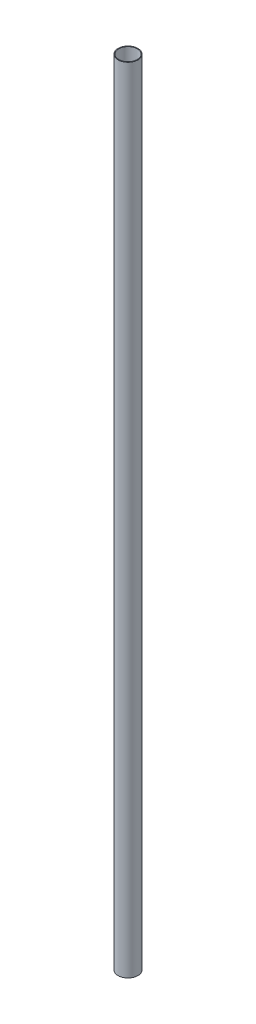
SolidWorks part; units mm, degrees
ref_plane "Front Plane" through (0, 0, 0) normal (0, 0, 1) x (1, 0, 0)
ref_plane "Top Plane" through (0, 0, 0) normal (0, 1, 0) x (1, 0, 0)
ref_plane "Right Plane" through (0, 0, 0) normal (1, 0, 0) x (0, 0, -1)
sketch "Sketch1" plane through (0, 0, 0) normal (0, 1, 0) x (1, 0, 0)
  circle A0 centre (0, 0) radius 3.25
  circle A1 centre (0, 0) radius 3.5
  dimension "D1" = 7
  dimension "D2" = 0.25
extrude "Boss-Extrude1" add sketch "Sketch1" along normal blind 278
equation "\"l2\"= 185"
equation "\"l1\"= 85"
equation "\"s1r\"= 2.14212rad"
equation "\"s2r\"= - 135deg"
equation "\"offset\"= 10mm"
equation "\"s1_len\"= 0.08255m"
equation "\"s2_len\" = 0mm"
equation "\"s1_anchor_dist\"= \"offset\" + \"l1\" + \"s1_len\""
equation "\"s2_anchor_dist\"= \"offset\" + \"l1\" + \"s2_len\"'this was: = \"offset\" + \"l1\" + \"s2_len\""
equation "\"carbon_fiber_plate_thickness\"=6"
equation "\"motor_to_motor_spacing\"=55.5"
equation "\"D1@Boss-Extrude1\"=\"l1\"+\"l2\"+8mm"
